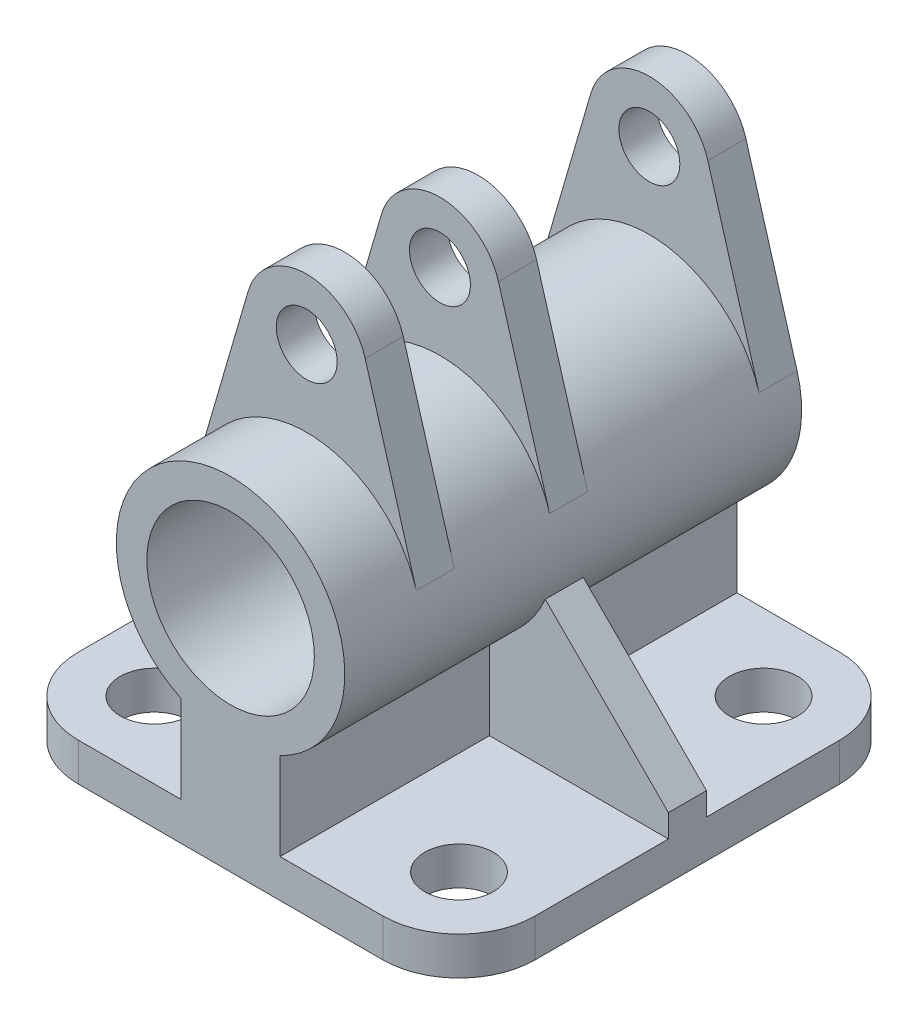
SolidWorks part; units mm, degrees
ref_plane "Спереди" through (0, 0, 0) normal (0, 0, 1) x (1, 0, 0)
ref_plane "Сверху" through (0, 0, 0) normal (0, 1, 0) x (1, 0, 0)
ref_plane "Справа" through (0, 0, 0) normal (1, 0, 0) x (0, 0, -1)
sketch "Эскиз1" plane through (0, 0, 0) normal (0, 0, 1) x (1, 0, 0)
  line L0 (13.8234, -5.8234) -> (30, -22)
  line L1 (30, -22) -> (30, -25)
  line L2 (30, -25) -> (6.5, -25)
  line L3 (6.5, -25) -> (6.5, -13.5185)
  line L4 (0, 0) -> (0, -39.2762) construction
  line L5 (-30, -30) -> (30, -30)
  line L6 (30, -30) -> (30, -25)
  line L7 (0, 0) -> (0, 45.2019) construction
  line L8 (7.68, 27.24) -> (14.4, 4.2)
  line L9 (-6.5, -25) -> (-6.5, -13.5185)
  line L10 (-30, -25) -> (-6.5, -25)
  line L11 (-30, -22) -> (-30, -25)
  line L12 (-13.8234, -5.8234) -> (-30, -22)
  line L13 (-7.68, 27.24) -> (-14.4, 4.2)
  line L14 (-30, -30) -> (-30, -25)
  circle A0 centre (0, 0) radius 11
  circle A1 centre (0, 0) radius 15
  arc A2 (7.68, 27.24) -> (-7.68, 27.24) centre (0, 25) ccw
  circle A3 centre (0, 25) radius 4
  point P15 (0, 33)
  point P27 (0, -30)
  dimension "D1" = 30
  dimension "D2" = 22
  dimension "D9" = 8
  dimension "D3" = 45
  dimension "D4" = 5
  dimension "D5" = 8
  dimension "D6" = 13
  dimension "D7" = 60
  dimension "D8" = 30
  dimension "D10" = 55
  dimension "D11" = 63
extrude "Бобышка-Вытянуть1" add sketch "Эскиз1" along normal mid plane 60 contours A1 L9 L10 L14 L5 L6 L2 L3 | A1 A0 region at (10.5584, -10.0485, 0) region at (0, -25.0787, 0)
extrude "Бобышка-Вытянуть2" add sketch "Эскиз1<3>" along normal mid plane 5 contours L8 A2 L13 A1 A3 | A1 L3 L2 L1 L0 | A1 L12 L11 L10 L9 region at (16.4394, -18.1684, 0) region at (-16.4394, -18.1684, 0) region at (0, 20.665, 0)
sketch "Эскиз1<3>" plane through (0, 0, 0) normal (0, 0, 1) x (1, 0, 0) same geometry as "Эскиз1"
extrude "Бобышка-Вытянуть3" add sketch "Эскиз1<6>" along normal blind 5 from offset 15 contours L8 A2 L13 A1 A3 region at (0, 20.665, 0)
sketch "Эскиз1<6>" plane through (0, 0, 0) normal (0, 0, 1) x (1, 0, 0) same geometry as "Эскиз1"
extrude "Бобышка-Вытянуть4" add sketch "Эскиз1<7>" along normal blind 5 from vertex contours L8 A2 L13 A1 A3 region at (0, 20.665, 0) starting at point (30, -30, -30)
sketch "Эскиз1<7>" plane through (0, 0, 0) normal (0, 0, 1) x (1, 0, 0) same geometry as "Эскиз1"
sketch "Эскиз2" plane through (0, -25, 0) normal (0, 1, 0) x (1, 0, 0)
  line L0 (0, 0) -> (57.1865, 0) construction
  line L3 (0, 56.0786) -> (0, -63.5322) construction
  circle A0 centre (20, 20) radius 4.5
  dimension "D1" = 9
  dimension "D2" = 20
  dimension "D3" = 20
extrude "Вырез-Вытянуть1" cut sketch "Эскиз2" against normal through all
mirror "Зеркальное отражение1" about plane through (0, 0, 0) normal (0, 0, 1) of "Вырез-Вытянуть1"
mirror "Зеркальное отражение2" about plane through (0, 0, 0) normal (1, 0, 0) of "Вырез-Вытянуть1", "Зеркальное отражение1"
fillet "Скругление1" radius 10 4 edges at (-30, -27.5, 30) (-30, -27.5, -30) (30, -27.5, -30) (30, -27.5, 30)
